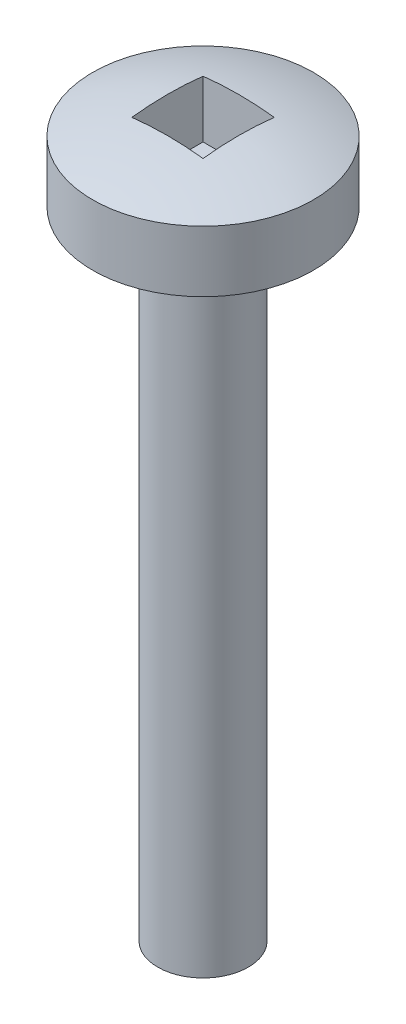
SolidWorks part; units mm, degrees
material "Cast Alloy Steel"
ref_plane "Front Plane" through (0, 0, 0) normal (0, 0, 1) x (1, 0, 0)
ref_plane "Top Plane" through (0, 0, 0) normal (0, 1, 0) x (1, 0, 0)
ref_plane "Right Plane" through (0, 0, 0) normal (1, 0, 0) x (0, 0, -1)
sketch "Sketch1" plane through (0, 0, 0) normal (0, 1, 0) x (1, 0, 0)
  circle A0 centre (0, 0) radius 1.1303
  dimension "D1" = 2.2606
extrude "threads" add sketch "Sketch1" against normal blind 15.875
sketch "Sketch2" plane through (0, 0, 0) normal (0, 1, 0) x (1, 0, 0)
  circle A0 centre (0, 0) radius 2.7559
  dimension "D1" = 5.5118
extrude "Head" add sketch "Sketch2" along normal blind 1.524
dome "HeadDome" faces to dome 1 distance 0.508 reverse direction no elliptical dome no face at (0, 1.524, 2.7559) parameters "D1"=0.508
ref_plane "DriverPlane" through (0, 2.032, 0) normal (0, 1, 0) x (1, 0, 0)
sketch "Sketch3" plane through (0, 2.032, 0) normal (0, 1, 0) x (1, 0, 0)
  line L1 (-0.889, -0.889) -> (0.889, -0.889)
  line L2 (-0.889, -0.889) -> (-0.889, 0.889)
  line L3 (-0.889, 0.889) -> (0.889, 0.889)
  line L4 (0.889, -0.889) -> (0.889, 0.889)
  line L5 (-0.889, -0.889) -> (0.889, 0.889) construction
  line L6 (-0.889, 0.889) -> (0.889, -0.889) construction
  point P0 (0, 0)
  dimension "D1" = 1.778
extrude "Driver" cut sketch "Sketch3" against normal blind 1.524
